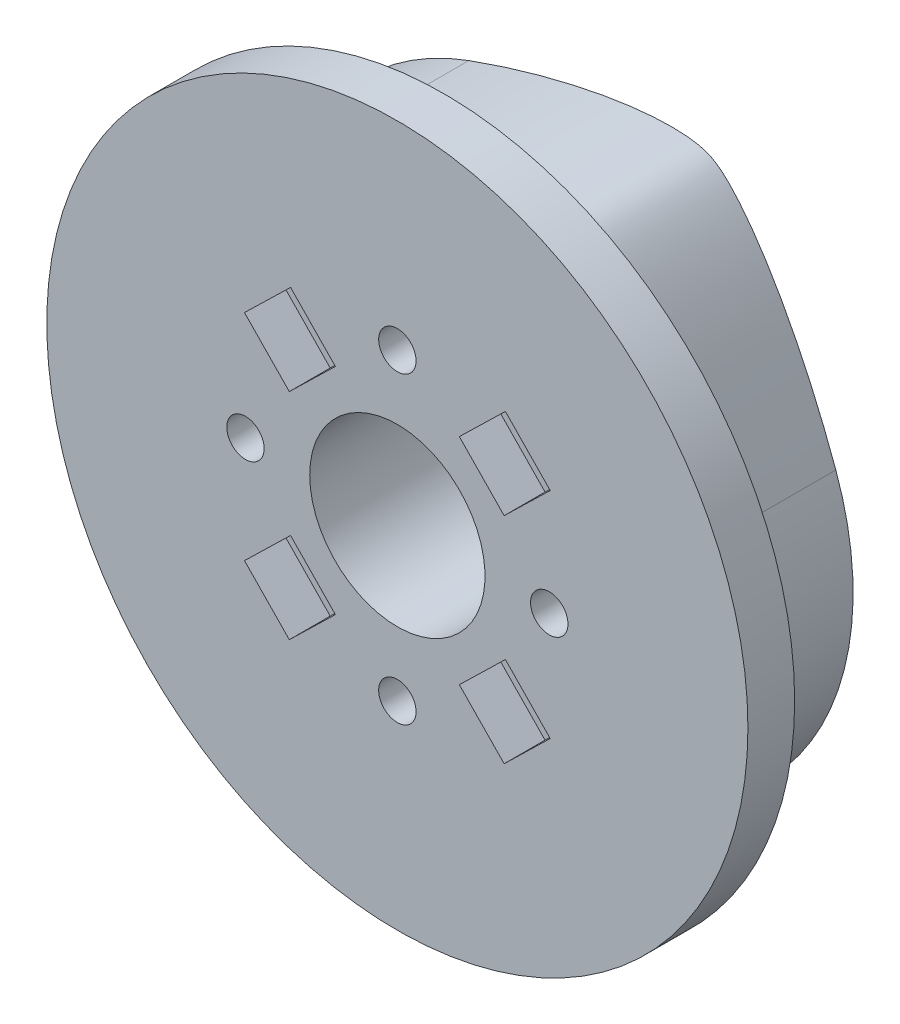
SolidWorks part; units mm, degrees
ref_plane "Front Plane" through (0, 0, 0) normal (1, 0, 0) x (0, 1, 0)
ref_plane "Top Plane" through (0, 0, 0) normal (0, 0, 1) x (0, 1, 0)
ref_plane "Right Plane" through (0, 0, 0) normal (0, 1, 0) x (-1, 0, 0)
sketch "Sketch1" plane through (0, 0, 0) normal (0, 0, 1) x (0, 1, 0)
  circle A0 centre (0, 0) radius 21
  circle A1 centre (0, 0) radius 13 construction
  circle A2 centre (0, 13) radius 1.6
  circle A3 centre (0, 13) radius 2.85
  circle A4 centre (13, 0) radius 2.85
  circle A5 centre (13, 0) radius 1.6
  circle A6 centre (0, -13) radius 2.85
  circle A7 centre (0, -13) radius 1.6
  circle A8 centre (-13, 0) radius 2.85
  circle A9 centre (-13, 0) radius 1.6
  point P19 (0, 0)
  dimension "D1" = 42
  dimension "D2" = 26
  dimension "D3" = 3.2
  dimension "D4" = 5.7
  dimension "D5" = 4
extrude "Boss-Extrude1" add sketch "Sketch1" along normal blind 10.5 contours A0 A8 A6 A4 A3 | A8 A9 | A3 A2 | A4 A5 | A6 A7 region at (0, 0, 0) region at (-13, -2.7694, 0) region at (0, 10.2306, 0) region at (13, -2.7694, 0) region at (0, -15.7694, 0)
sketch "Sketch2" plane through (0, 0, 0) normal (0, 0, -1) x (1, 0, 0)
  line L0 (0, 0) -> (0, 29) construction
  line L1 (0, 0) -> (12.2559, -26.2829) construction
  line L2 (0, 0) -> (-9.9186, -27.2511) construction
  line L3 (0, 0) -> (27.2511, -9.9186) construction
  line L4 (10.5953, -27.0573) -> (-25.657, -43.962) construction
  line L5 (30.3658, -37.1246) -> (-82.3973, 3.9178) construction
  line L6 (37.1246, 30.3658) -> (-3.9178, -82.3973) construction
  circle A0 centre (0, 0) radius 29 construction
  circle A1 centre (0, 0) radius 24.5
  spline S0 degree 3 poles (-8.3795, -23.0225) (0.0777, -26.1007) (9.6125, -27.5644) (14.9368, -25.0817) (19.9443, -16.8367) (23.0225, -8.3795) knots 0 0 0 0 0.45 0.55 1 1 1 1
  circle M5 centre (0, 0) radius 21
  dimension "D1" = 58
  dimension "D2" = 49
  dimension "D6" = 20
  dimension "D7" = 30
  dimension "D8" = 30
  dimension "D3" = 155
  dimension "D4" = 45
  dimension "D5" = 45
  dimension "D9" = 90
  dimension "D10" = 90
  dimension "D11" = 90
extrude "Boss-Extrude3" add sketch "Sketch2" against normal up to surface (10.5 mm away) contours A1 M5 | A1 S0 region at (23.4454, 4.134, 0) region at (10.6894, 22.9008, 0) up to face at (21, 0, 10.5)
sketch "Sketch4" plane through (0, 0, 10.5) normal (0, 0, 1) x (1, 0, 0)
  circle A0 centre (0, 0) radius 30
  circle A5 centre (-13, 0) radius 1.6
  circle A6 centre (0, 13) radius 1.6
  circle A7 centre (13, 0) radius 1.6
  circle A8 centre (0, -13) radius 1.6
  dimension "D1" = 60
extrude "Boss-Extrude5" add sketch "Sketch4" along normal blind 4
sketch "Sketch3" plane through (0, 0, 0) normal (0, 0, -1) x (1, 0, 0)
  circle A0 centre (0, 0) radius 21
  circle A5 centre (-13, 0) radius 1.6
  circle A6 centre (0, 13) radius 1.6
  circle A7 centre (13, 0) radius 1.6
  circle A8 centre (0, -13) radius 1.6
  dimension "D1" = 42
extrude "Boss-Extrude4" add sketch "Sketch3" along normal blind 0.5
sketch "Sketch6" plane through (0, 0, -0.5) normal (0, 0, -1) x (1, 0, 0)
  line L0 (15.75, -2.75) -> (10.25, -2.75)
  line L1 (-2.75, 15.75) -> (2.75, 15.75)
  line L2 (-2.75, 15.75) -> (-2.75, 10.25)
  line L3 (-2.75, 10.25) -> (2.75, 10.25)
  line L4 (2.75, 15.75) -> (2.75, 10.25)
  line L5 (-2.75, 15.75) -> (2.75, 10.25) construction
  line L6 (-2.75, 10.25) -> (2.75, 15.75) construction
  line L7 (10.25, 2.75) -> (10.25, -2.75)
  line L8 (15.75, 2.75) -> (10.25, 2.75)
  line L9 (15.75, 2.75) -> (15.75, -2.75)
  line L10 (15.75, 2.75) -> (10.25, -2.75) construction
  line L11 (10.25, 2.75) -> (15.75, -2.75) construction
  line L12 (-2.75, -15.75) -> (-2.75, -10.25)
  line L13 (2.75, -10.25) -> (-2.75, -10.25)
  line L14 (2.75, -15.75) -> (2.75, -10.25)
  line L15 (2.75, -15.75) -> (-2.75, -15.75)
  line L16 (2.75, -15.75) -> (-2.75, -10.25) construction
  line L17 (2.75, -10.25) -> (-2.75, -15.75) construction
  line L18 (-15.75, 2.75) -> (-10.25, 2.75)
  line L19 (-10.25, -2.75) -> (-10.25, 2.75)
  line L20 (-15.75, -2.75) -> (-10.25, -2.75)
  line L21 (-15.75, -2.75) -> (-15.75, 2.75)
  line L22 (-15.75, -2.75) -> (-10.25, 2.75) construction
  line L23 (-10.25, -2.75) -> (-15.75, 2.75) construction
  point P0 (0, 13)
  point P21 (0, 0)
  dimension "D1" = 5.5
  dimension "D2" = 5.5
extrude "Cut-Extrude2" cut sketch "Sketch6" against normal offset from surface (3.5 mm away) 11.5 up to face at (14.6, 0, 14.5)
sketch "Sketch7" plane through (0, 0, 14.5) normal (0, 0, 1) x (1, 0, 0)
  line L0 (0, 0) -> (9.1924, 9.1924) construction
  line L1 (9.2456, 13.0807) -> (5.3041, 9.2465)
  line L2 (9.2456, 13.0807) -> (13.0807, 9.1383)
  line L3 (5.3041, 9.2465) -> (9.1392, 5.3041)
  line L4 (13.0807, 9.1383) -> (9.1392, 5.3041)
  line L5 (9.2456, 13.0807) -> (9.1392, 5.3041) construction
  line L6 (5.3041, 9.2465) -> (13.0807, 9.1383) construction
  line L7 (9.1383, -13.0807) -> (5.3041, -9.1392)
  line L8 (9.2465, -5.3041) -> (5.3041, -9.1392)
  line L9 (13.0807, -9.2456) -> (9.2465, -5.3041)
  line L10 (13.0807, -9.2456) -> (9.1383, -13.0807)
  line L11 (13.0807, -9.2456) -> (5.3041, -9.1392) construction
  line L12 (9.2465, -5.3041) -> (9.1383, -13.0807) construction
  line L13 (-13.0807, -9.1383) -> (-9.1392, -5.3041)
  line L14 (-5.3041, -9.2465) -> (-9.1392, -5.3041)
  line L15 (-9.2456, -13.0807) -> (-5.3041, -9.2465)
  line L16 (-9.2456, -13.0807) -> (-13.0807, -9.1383)
  line L17 (-9.2456, -13.0807) -> (-9.1392, -5.3041) construction
  line L18 (-5.3041, -9.2465) -> (-13.0807, -9.1383) construction
  line L19 (-9.1383, 13.0807) -> (-5.3041, 9.1392)
  line L20 (-9.2465, 5.3041) -> (-5.3041, 9.1392)
  line L21 (-13.0807, 9.2456) -> (-9.2465, 5.3041)
  line L22 (-13.0807, 9.2456) -> (-9.1383, 13.0807)
  line L23 (-13.0807, 9.2456) -> (-5.3041, 9.1392) construction
  line L24 (-9.2465, 5.3041) -> (-9.1383, 13.0807) construction
  circle A0 centre (0, 0) radius 13 construction
  circle A1 centre (9.1924, 9.1924) radius 1.6
  circle A10 centre (9.1924, -9.1924) radius 1.6
  circle A11 centre (-9.1924, -9.1924) radius 1.6
  circle A12 centre (-9.1924, 9.1924) radius 1.6
  point P18 (0, 0)
  point P34 (0, 0)
  dimension "D1" = 3.2
  dimension "D2" = 5.4988
  dimension "D3" = 5.5
extrude "Cut-Extrude3" cut sketch "Sketch7" against normal through all contours A1 | A12 | A11 | A10 region at (9.1924, 9.1924, 14.5) region at (9.1924, -9.1924, 14.5) region at (-9.1924, -9.1924, 14.5) region at (-9.1924, 9.1924, 14.5)
extrude "Cut-Extrude4" cut sketch "Sketch7<3>" against normal blind 3.5
sketch "Sketch7<3>" plane through (0, 0, 14.5) normal (0, 0, 1) x (1, 0, 0) same geometry as "Sketch7"
sketch "Sketch8" plane through (0, 0, -0.5) normal (0, 0, -1) x (1, 0, 0)
  circle A0 centre (0, 0) radius 7.5
  dimension "D1" = 15
extrude "Cut-Extrude5" cut sketch "Sketch8" against normal through all
